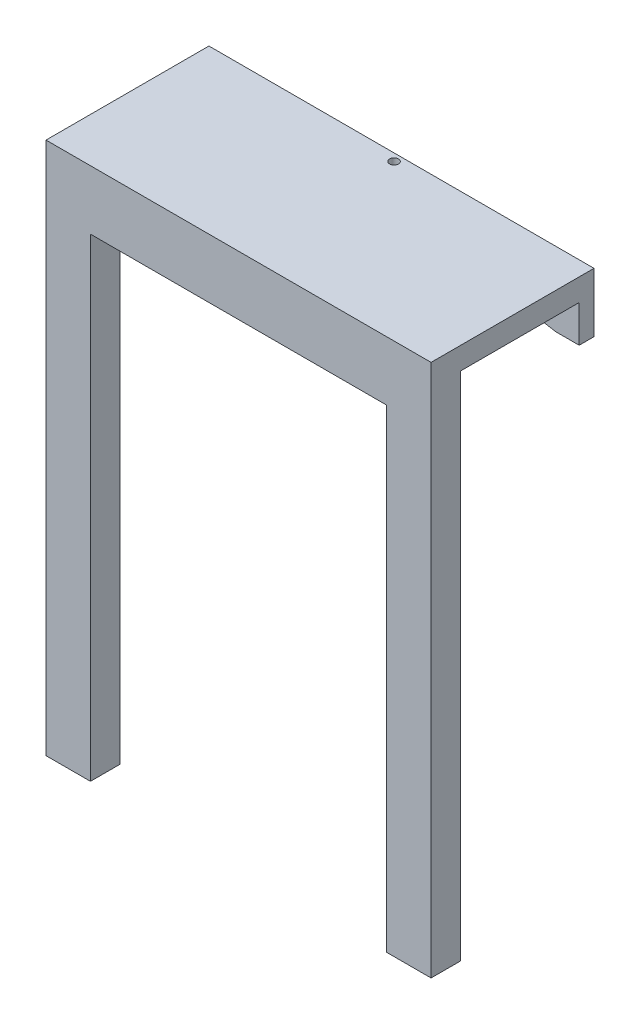
SolidWorks part; units mm, degrees
ref_plane "Front Plane" through (0, 0, 0) normal (0, 0, 1) x (1, 0, 0)
ref_plane "Top Plane" through (0, 0, 0) normal (0, 1, 0) x (1, 0, 0)
ref_plane "Right Plane" through (0, 0, 0) normal (1, 0, 0) x (0, 0, -1)
sketch "Sketch1" plane through (0, 0, 0) normal (0, 0, 1) x (1, 0, 0)
  line L1 (-82.55, -114.3) -> (82.55, -114.3)
  line L2 (-82.55, -114.3) -> (-82.55, 114.3)
  line L3 (-82.55, 114.3) -> (82.55, 114.3)
  line L4 (82.55, -114.3) -> (82.55, 114.3)
  line L5 (-82.55, -114.3) -> (82.55, 114.3) construction
  line L6 (-82.55, 114.3) -> (82.55, -114.3) construction
  point P0 (0, 0)
  dimension "D1" = 228.6
  dimension "D2" = 165.1
extrude "Boss-Extrude1" add sketch "Sketch1" along normal blind 12.7
sketch "Sketch2" plane through (0, 0, 12.7) normal (0, 0, 1) x (1, 0, 0)
  line L0 (-82.55, -114.3) -> (82.55, -114.3) construction
  line L1 (-63.5, -114.3) -> (63.5, -114.3)
  line L2 (-63.5, -114.3) -> (-63.5, 88.9)
  line L3 (-63.5, 88.9) -> (63.5, 88.9)
  line L4 (63.5, -114.3) -> (63.5, 88.9)
  line L5 (-82.55, 114.3) -> (-82.55, -114.3) construction
  dimension "D1" = 203.2
  dimension "D2" = 127
  dimension "D3" = 19.05
extrude "Cut-Extrude1" cut sketch "Sketch2" against normal through all
sketch "Sketch3" plane through (0, 0, 0) normal (0, 0, -1) x (-1, 0, 0)
  line L0 (82.55, 114.3) -> (82.55, -114.3) construction
  line L1 (-82.55, 114.3) -> (82.55, 114.3)
  line L2 (-82.55, 114.3) -> (-82.55, 104.775)
  line L3 (-82.55, 104.775) -> (82.55, 104.775)
  line L4 (82.55, 114.3) -> (82.55, 104.775)
  dimension "D1" = 9.525
extrude "Boss-Extrude2" add sketch "Sketch3" along normal blind 57.15
sketch "Sketch4" plane through (0, 0, -57.15) normal (0, 0, -1) x (-1, 0, 0)
  line L7 (-82.55, 104.775) -> (-63.5, 104.775)
  line L8 (-82.55, 104.775) -> (-82.55, 88.9)
  line L9 (-82.55, 88.9) -> (-63.5, 88.9)
  line L10 (-63.5, 104.775) -> (-63.5, 88.9)
  dimension "D1" = 15.875
  dimension "D2" = 19.05
extrude "Boss-Extrude3" add sketch "Sketch4" against normal blind 6.35
mirror "Mirror1" about plane through (0, 0, 0) normal (1, 0, 0) of "Boss-Extrude3"
sketch "Sketch5" plane through (0, 0, -57.15) normal (0, 0, -1) x (-1, 0, 0)
  line L5 (-72.5032, 88.9) -> (-63.5, 90.4875)
  line L6 (-82.55, 88.9) -> (-63.5, 88.9) construction
  line L7 (-63.5, 88.9) -> (-63.5, 104.775) construction
  line L8 (-63.5, 90.4875) -> (-63.5, 88.9)
  line L9 (-63.5, 88.9) -> (-72.5032, 88.9)
  dimension "D1" = 1.5875
  dimension "D2" = 80
extrude "Cut-Extrude2" cut sketch "Sketch5" against normal up to next
mirror "Mirror2" about plane through (0, 0, 0) normal (1, 0, 0) of "Cut-Extrude2"
sketch "Sketch6" plane through (0, 114.3, 0) normal (0, 1, 0) x (1, 0, 0)
  line L0 (-82.55, 57.15) -> (82.55, 57.15) construction
  circle A0 centre (0, 53.975) radius 1.8986
  dimension "D1" = 3.7973
  dimension "D2" = 3.175
extrude "Cut-Extrude3" cut sketch "Sketch6" against normal up to next
